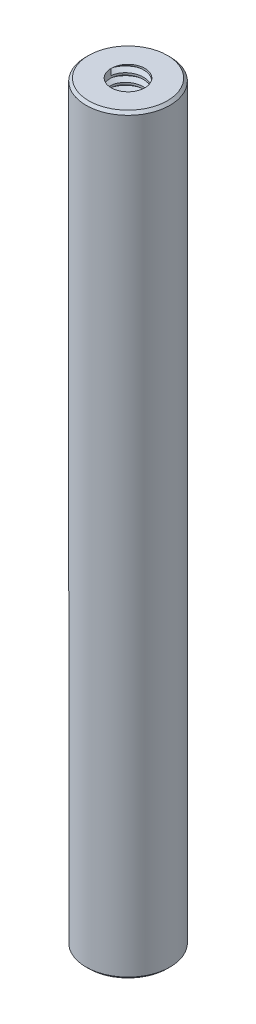
SolidWorks part; units mm, degrees
material "6061-T6 (SS)"
ref_plane "Alzado" through (0, 0, 0) normal (0, 0, 1) x (1, 0, 0)
ref_plane "Planta" through (0, 0, 0) normal (0, 1, 0) x (1, 0, 0)
ref_plane "Vista lateral" through (0, 0, 0) normal (1, 0, 0) x (0, 0, -1)
sketch "Croquis2" plane through (0, 0, 0) normal (0, 1, 0) x (1, 0, 0)
  circle A0 centre (0, 0) radius 6.35
  dimension "D1" = 12.7
extrude "Saliente-Extruir1" add sketch "Croquis2" along normal mid plane 113.7313
chamfer "Chaflán1" distance 0.3969 angle 45 2 edges at (0, -56.8657, 6.35) (0, 56.8657, 6.35)
sketch "Croquis3" plane through (0, 0, 0) normal (0, 1, 0) x (1, 0, 0)
  circle A0 centre (0, 0) radius 2.5527
  dimension "D1" = 5.1054
extrude "Tap Hole 1" cut sketch "Croquis3" against normal blind 19.05 from surface starting at face at (0, 56.8657, 5.9531)
extrude "Tap Hole 2" cut sketch "Croquis3<2>" along normal blind 19.05 from surface starting at face at (0, -56.8657, 5.9531)
sketch "Croquis3<2>" plane through (0, 0, 0) normal (0, 1, 0) x (1, 0, 0) same geometry as "Croquis3"
sketch "Croquis4" plane through (0, 0, 0) normal (0, 1, 0) x (1, 0, 0)
  circle A0 centre (0, 0) radius 3.2639
  dimension "D1" = 6.5278
extrude "Clearance Hole" [suppressed] cut sketch "Croquis4" against normal through all both and the other way through all
thread "Rosca1" pitch 1.27 method cut profile "Perfil de rosca1" start angle 0, offset 0, length 0, pitch 1.27, diameter 5.1054
ref_plane "Plano1" through (-2.5527, 56.8657, 0) normal (0, 0, 1) x (-1, 0, 0)
sketch "Perfil de rosca1" plane through (-2.5527, 56.8657, 0) normal (0, 0, 1) x (-1, 0, 0)
  line L0 (0, 0) -> (0, 1.27) construction
  line L1 (0, 0) -> (0.6874, 0.3969)
  line L2 (0.6874, 0.3969) -> (0.6874, 0.5556)
  line L3 (0.6874, 0.5556) -> (0, 0.9525)
  line L4 (0.6874, 0.4762) -> (0, 0.4762) construction
  line L11 (0, 0) -> (0, 0.9525)
  point P2 (0, 0)
  dimension "Pitch" = 1.27
  dimension "Profile_Angle" = 60
  dimension "Profile_Land" = 0.1588
  dimension "Profile_Height" = 0.6874
thread "Rosca2" pitch 1.27 method cut profile "Perfil de rosca2" start angle 0, offset 0, length 0, pitch 1.27, diameter 5.1054
ref_plane "Plano2" through (2.5527, -56.8657, 0) normal (0, 0, 1) x (1, 0, 0)
sketch "Perfil de rosca2" plane through (2.5527, -56.8657, 0) normal (0, 0, 1) x (1, 0, 0)
  line L0 (0, 0) -> (0, 1.27) construction
  line L1 (0, 0) -> (0.6874, 0.3969)
  line L2 (0.6874, 0.3969) -> (0.6874, 0.5556)
  line L3 (0.6874, 0.5556) -> (0, 0.9525)
  line L4 (0.6874, 0.4762) -> (0, 0.4762) construction
  line L11 (0, 0) -> (0, 0.9525)
  point P2 (0, 0)
  dimension "Pitch" = 1.27
  dimension "Profile_Angle" = 60
  dimension "Profile_Land" = 0.1588
  dimension "Profile_Height" = 0.6874
equation "\"OD\"= 0.5pulgadas"
equation "\"Largo\"= 4.47761024pulgadas"
equation "\"Tap Hole\"= IIF ( \"OD\" = 0.375pulgadas , 0.1590pulgadas , 0.201pulgadas )"
equation "\"Spacer Hole\"= IIF ( \"OD\" = 0.375pulgadas , 0.196pulgadas , 0.257pulgadas )"
equation "\"D1@Croquis2\"=\"OD\""
equation "\"D1@Saliente-Extruir1\"=\"Largo\""
equation "\"D1@Croquis3\"=\"Tap Hole\""
equation "\"D1@Croquis4\"=\"Spacer Hole\""
